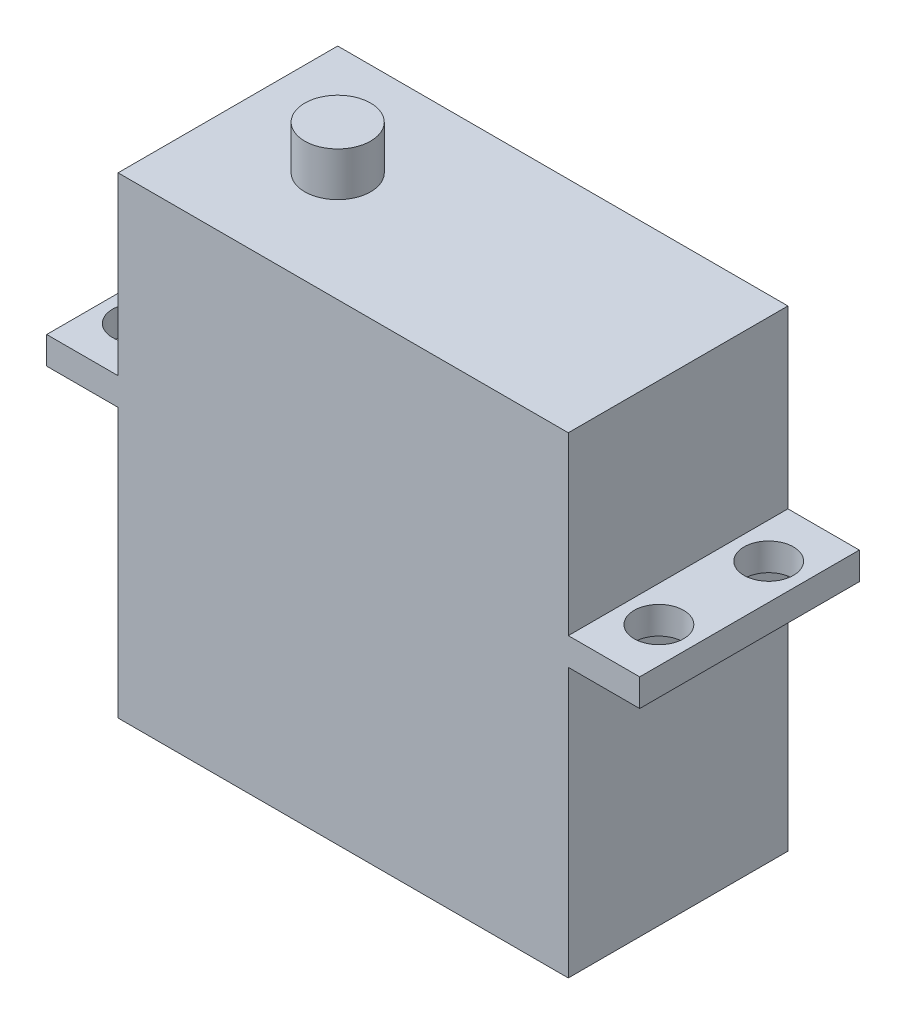
SolidWorks part; units mm, degrees
ref_plane "Piano frontale" through (0, 0, 0) normal (0, 0, 1) x (1, 0, 0)
ref_plane "Piano superiore" through (0, 0, 0) normal (0, 1, 0) x (1, 0, 0)
ref_plane "Piano destro" through (0, 0, 0) normal (1, 0, 0) x (0, 0, -1)
sketch "Schizzo1" plane through (0, 0, 0) normal (0, 1, 0) x (1, 0, 0)
  line L1 (-10, 10) -> (31, 10)
  line L2 (-10, 10) -> (-10, -10)
  line L3 (-10, -10) -> (31, -10)
  line L4 (31, 10) -> (31, -10)
  dimension "D1" = 41
  dimension "D2" = 20
  dimension "D3" = 10
  dimension "D4" = 10
extrude "Estrusione-Estrusione1" add sketch "Schizzo1" along normal blind 43 contours L2 L3 L4 L1
sketch "Schizzo2" plane through (0, 43, 0) normal (0, 1, 0) x (1, 0, 0)
  circle A0 centre (0, 0) radius 3
  dimension "D1" = 6
extrude "Estrusione-Estrusione4" add sketch "Schizzo2" along normal blind 4 contours A0
sketch "Schizzo4" plane through (0, 0, 0) normal (0, 0, 1) x (1, 0, 0)
  line L0 (0, -2.4685) -> (0, 49.6424) construction
  line L1 (-16.5, 27) -> (37.5, 27)
  line L2 (-16.5, 27) -> (-16.5, 24.5)
  line L3 (-16.5, 24.5) -> (37.5, 24.5)
  line L4 (37.5, 27) -> (37.5, 24.5)
  line L5 (-25.9485, 0) -> (47.7444, 0) construction
  dimension "D1" = 54
  dimension "D2" = 2.5
  dimension "D3" = 16.5
  dimension "D4" = 24.5
extrude "Estrusione-Estrusione5" add sketch "Schizzo4" along normal blind 10 and the other way blind 10 contours L1 L4 L3 L2
sketch "Schizzo5" plane through (0, 27, 0) normal (0, 1, 0) x (1, 0, 0)
  line L0 (-21.0898, 0) -> (42.1671, 0) construction
  line L1 (10.5, -13.6168) -> (10.5, 13.662) construction
  circle A0 centre (-13.2503, 5) radius 2.25
  circle A1 centre (-13.2503, -5) radius 2.25
  circle A2 centre (34.2503, -5) radius 2.25
  circle A3 centre (34.2503, 5) radius 2.25
  point P13 (0, 0)
  dimension "D2" = 4.5
  dimension "D3" = 47.5006
  dimension "D4" = 10.5
  dimension "D1" = 5
hole_wizard "Foro per Vite M1.6-1" positions "Schizzo6" profile "Schizzo7" hole size "M1.6" standard "Ansi Metric" end condition through all
sketch "Schizzo6" plane through (0, 27, 0) normal (0, 1, 0) x (1, 0, 0)
  point P0 (-13.2503, 5)
  point P3 (-13.2503, 5)
  point P5 (-13.2503, -5)
  point P8 (34.2503, 5)
  point P11 (34.2503, -5)
sketch "Schizzo7" plane through (-13.2503, 27, -5) normal (1, 0, 0) x (0, 0, 1)
  line L0 (0, 0) -> (0, 27)
  line L1 (0, 27) -> (2.25, 27)
  line L2 (2.25, 27) -> (2.25, 0)
  line L5 (2.25, 0) -> (0, 0)
  line L11 (0, -6.35) -> (0, 107.95) construction
  dimension "Thru Hole Dia." = 4.5
  dimension "Thru Hole Depth" = 27
sketch "Schizzo8" plane through (0, 43, 0) normal (0, 1, 0) x (1, 0, 0)
  line L0 (0, 0) -> (0, 10) construction
  line L1 (-10, 10) -> (31, 10) construction
